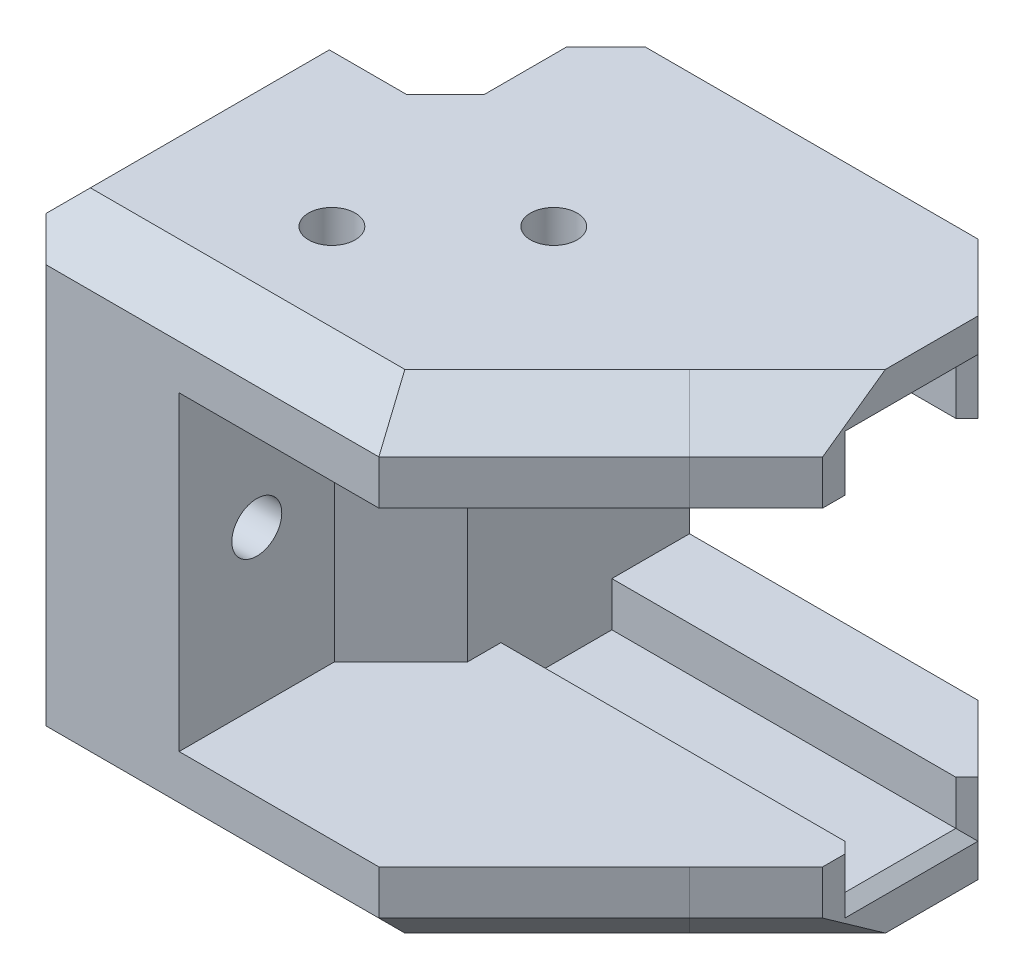
SolidWorks part; units mm, degrees
ref_plane "Front Plane" through (0, 0, 0) normal (0, 0, 1) x (1, 0, 0)
ref_plane "Top Plane" through (0, 0, 0) normal (0, 1, 0) x (1, 0, 0)
ref_plane "Right Plane" through (0, 0, 0) normal (1, 0, 0) x (0, 0, -1)
sketch "Sketch9" plane through (0, 0, 0) normal (0, 1, 0) x (1, 0, 0)
  line L1 (0, 0) -> (36, 0)
  line L2 (0, 0) -> (0, 36)
  line L3 (0, 36) -> (36, 36)
  line L4 (36, 0) -> (36, 36)
  dimension "D1" = 36
  dimension "D2" = 36
extrude "Boss-Extrude1" add sketch "Sketch9" along normal blind 40
chamfer "Chamfer2" distance 18 angle 45 1 edges at (0, 20, -36)
sketch "Sketch10" plane through (36, 0, 0) normal (1, 0, 0) x (0, 0, -1)
  line L4 (0, 0) -> (36, 0)
  line L5 (36, 0) -> (36, 40)
  line L6 (36, 40) -> (0, 40)
  line L7 (0, 40) -> (0, 0)
  line L8 (0, 0) -> (36, 0)
  line L9 (36, 0) -> (36, 40)
  line L10 (36, 40) -> (0, 40)
  line L11 (0, 40) -> (0, 0)
  dimension "D1" = 0
extrude "Boss-Extrude2" add sketch "Sketch10" along normal blind 8
sketch "Sketch12" plane through (0, 0, 0) normal (0, 0, 1) x (1, 0, 0)
  line L4 (0, 0) -> (44, 0)
  line L5 (44, 0) -> (44, 40)
  line L6 (44, 40) -> (0, 40)
  line L7 (0, 40) -> (0, 0)
  line L8 (0, 0) -> (44, 0)
  line L9 (44, 0) -> (44, 40)
  line L10 (44, 40) -> (0, 40)
  line L11 (0, 40) -> (0, 0)
  dimension "D1" = 0
extrude "Boss-Extrude3" add sketch "Sketch12" along normal blind 8
chamfer "Chamfer3" distance 18 angle 45 2 edges at (0, 20, 8) (44, 20, -36)
chamfer "Chamfer4" distance 6 angle 45 1 edges at (44, 20, 8)
sketch "Sketch13" plane through (23, 0, 23) normal (0.7071, 0, 0.7071) x (0.7071, 0, -0.7071)
  line L0 (7.0711, 40) -> (7.0711, 0) construction
  line L1 (7.0711, 32) -> (43.8406, 32)
  line L2 (7.0711, 32) -> (7.0711, 12)
  line L3 (7.0711, 12) -> (43.8406, 12)
  line L4 (43.8406, 32) -> (43.8406, 12)
  line L5 (43.8406, 0) -> (43.8406, 40) construction
  dimension "D1" = 8
  dimension "D2" = 20
extrude "Cut-Extrude6" cut sketch "Sketch13" against normal up to vertex (39.598 mm away) up to point (0, 40, -10)
sketch "Sketch22" plane through (-9, 0, -9) normal (-0.7071, 0, -0.7071) x (-0.7071, 0, 0.7071)
  line L0 (-38.1838, 40) -> (-12.7279, 40) construction
  circle A0 centre (-15.4558, 36) radius 2.1
  circle A1 centre (-35.4558, 36) radius 2.1
  circle A2 centre (-35.4558, 4) radius 2.1
  circle A3 centre (-15.4558, 4) radius 2.1
  point P16 (-25.4558, 40)
  dimension "D5" = 4.2
  dimension "D1" = 4
  dimension "D2" = 20
  dimension "D3" = 10
  dimension "D4" = 32
extrude "Cut-Extrude13" cut sketch "Sketch22" against normal blind 6
sketch "Sketch23" plane through (0, 40, 0) normal (0, 1, 0) x (1, 0, 0)
  line L0 (26, 36) -> (44, 36)
  line L1 (44, 36) -> (44, 18)
  line L2 (26, 36) -> (44, 18)
extrude "Boss-Extrude7" add sketch "Sketch23" against normal blind 8
sketch "Sketch24" plane through (0, 0, 0) normal (0, -1, 0) x (-1, 0, 0)
  line L0 (-44, 18) -> (-26, 36)
  line L1 (-26, 36) -> (-44, 36)
  line L2 (-44, 36) -> (-44, 18)
extrude "Boss-Extrude8" add sketch "Sketch24" against normal up to surface (12 mm away) up to face at (28.3333, 12, -7.6667)
sketch "Sketch25" plane through (0, 40, 0) normal (0, 1, 0) x (1, 0, 0)
  line L7 (18, -8) -> (38, -8)
  line L8 (38, -8) -> (44, -2)
  line L9 (44, -2) -> (44, 36)
  line L10 (44, 36) -> (18, 36)
  line L11 (18, 36) -> (0, 18)
  line L12 (0, 18) -> (0, 10)
  line L13 (0, 10) -> (18, -8)
  line L14 (18, -8) -> (38, -8)
  line L15 (38, -8) -> (44, -2)
  line L16 (44, -2) -> (44, 36)
  line L17 (44, 36) -> (18, 36)
  line L18 (18, 36) -> (0, 18)
  line L19 (0, 18) -> (0, 10)
  line L20 (0, 10) -> (18, -8)
  dimension "D1" = 0
extrude "Boss-Extrude9" add sketch "Sketch25" along normal blind 4
sketch "Sketch26" plane through (0, 32, 0) normal (0, -1, 0) x (-1, 0, 0)
  line L6 (-44, 36) -> (-44, -2)
  line L7 (-44, -2) -> (-38, -8)
  line L8 (-38, -8) -> (-18, -8)
  line L9 (-18, -8) -> (0, 10)
  line L10 (0, 10) -> (-26, 36)
  line L11 (-26, 36) -> (-44, 36)
  line L12 (-44, 36) -> (-44, -2)
  line L13 (-44, -2) -> (-38, -8)
  line L14 (-38, -8) -> (-18, -8)
  line L15 (-18, -8) -> (0, 10)
  line L16 (0, 10) -> (-26, 36)
  line L17 (-26, 36) -> (-44, 36)
  dimension "D1" = 0
extrude "Cut-Extrude14" cut sketch "Sketch26" against normal blind 4
sketch "Sketch27" plane through (0, 12, 0) normal (0, 1, 0) x (1, 0, 0)
  line L6 (44, -2) -> (44, 36)
  line L7 (44, 36) -> (26, 36)
  line L8 (26, 36) -> (0, 10)
  line L9 (0, 10) -> (18, -8)
  line L10 (18, -8) -> (38, -8)
  line L11 (38, -8) -> (44, -2)
  line L12 (44, -2) -> (44, 36)
  line L13 (44, 36) -> (26, 36)
  line L14 (26, 36) -> (0, 10)
  line L15 (0, 10) -> (18, -8)
  line L16 (18, -8) -> (38, -8)
  line L17 (38, -8) -> (44, -2)
  dimension "D1" = 0
extrude "Cut-Extrude15" cut sketch "Sketch27" against normal blind 4
sketch "Sketch28" plane through (0, 0, -36) normal (0, 0, -1) x (-1, 0, 0)
  line L1 (-26, 36) -> (-22, 36)
  line L2 (-26, 36) -> (-26, 8)
  line L3 (-26, 8) -> (-22, 8)
  line L4 (-22, 36) -> (-22, 8)
  dimension "D1" = 4
extrude "Cut-Extrude16" cut sketch "Sketch28" against normal through all
sketch "Sketch30" plane through (0, 8, 0) normal (0, 1, 0) x (1, 0, 0)
  line L0 (0, 10) -> (22, 10)
  line L1 (22, 10) -> (22, 32)
  line L2 (22, 32) -> (0, 10)
extrude "Boss-Extrude11" add sketch "Sketch30" along normal up to surface (28 mm away) up to face at (19.5314, 36, -18.602)
sketch "Sketch31" plane through (44, 0, 0) normal (1, 0, 0) x (0, 0, -1)
  line L1 (19, 40) -> (29, 40)
  line L2 (19, 40) -> (19, 4)
  line L3 (19, 4) -> (29, 4)
  line L4 (29, 40) -> (29, 4)
  dimension "D1" = 10
  dimension "D2" = 7
  dimension "D3" = 4
  dimension "D4" = 4
extrude "Cut-Extrude17" cut sketch "Sketch31" against normal up to surface (22 mm away) up to face at (22, 22, -23)
sketch "Sketch32" plane through (0, 0, 0) normal (0, -1, 0) x (-1, 0, 0)
  line L0 (-44, -2) -> (-44, 36) construction
  line L1 (0, 10) -> (-44, 10)
  line L2 (0, 10) -> (0, -8.0269)
  line L3 (0, -8.0269) -> (-44, -8.0269)
  line L4 (-44, 10) -> (-44, -8.0269)
extrude "Cut-Extrude18" cut sketch "Sketch32" against normal through all
sketch "Sketch33" plane through (44, 0, 0) normal (1, 0, 0) x (0, 0, -1)
  line L8 (10, 8) -> (10, 0)
  line L9 (10, 0) -> (36, 0)
  line L10 (36, 0) -> (36, 8)
  line L11 (36, 8) -> (29, 8)
  line L12 (29, 8) -> (29, 4)
  line L13 (29, 4) -> (19, 4)
  line L14 (19, 4) -> (19, 8)
  line L15 (19, 8) -> (10, 8)
  line L16 (10, 8) -> (10, 0)
  line L17 (10, 0) -> (36, 0)
  line L18 (36, 0) -> (36, 8)
  line L19 (36, 8) -> (29, 8)
  line L20 (29, 8) -> (29, 4)
  line L21 (29, 4) -> (19, 4)
  line L22 (19, 4) -> (19, 8)
  line L23 (19, 8) -> (10, 8)
  dimension "D1" = 0
extrude "Boss-Extrude12" add sketch "Sketch33" along normal blind 10
sketch "Sketch35" plane through (44, 0, 0) normal (1, 0, 0) x (0, 0, -1)
  line L8 (10, 44) -> (10, 36)
  line L9 (10, 36) -> (19, 36)
  line L10 (19, 36) -> (19, 40)
  line L11 (19, 40) -> (29, 40)
  line L12 (29, 40) -> (29, 36)
  line L13 (29, 36) -> (36, 36)
  line L14 (36, 36) -> (36, 44)
  line L15 (36, 44) -> (10, 44)
  line L16 (10, 44) -> (10, 36)
  line L17 (10, 36) -> (19, 36)
  line L18 (19, 36) -> (19, 40)
  line L19 (19, 40) -> (29, 40)
  line L20 (29, 40) -> (29, 36)
  line L21 (29, 36) -> (36, 36)
  line L22 (36, 36) -> (36, 44)
  line L23 (36, 44) -> (10, 44)
  dimension "D1" = 0
extrude "Boss-Extrude13" add sketch "Sketch35" along normal blind 10
chamfer "Chamfer5" distance 6 angle 45 4 edges at (54, 4, -36) (54, 4, -10) (54, 40, -36) (54, 40, -10)
sketch "Sketch36" plane through (0, 44, 0) normal (0, 1, 0) x (1, 0, 0)
  line L0 (14, 32) -> (14, 26)
  line L1 (18, 36) -> (0, 18) construction
  line L2 (14, 26) -> (10, 22)
  line L3 (10, 22) -> (4, 22)
  line L4 (4, 22) -> (14, 32)
  dimension "D1" = 4
  dimension "D2" = 4
  dimension "D3" = 6
extrude "Cut-Extrude19" cut sketch "Sketch36" against normal through all
chamfer "Chamfer6" distance 6 angle 45 1 edges at (22, 22, -10)
sketch "Sketch37" plane through (22, 0, 0) normal (1, 0, 0) x (0, 0, -1)
  circle A0 centre (24, 31) radius 2.8
  circle A1 centre (24, 13) radius 2.8
  dimension "D4" = 5.6
  dimension "D1" = 5
  dimension "D2" = 9
  dimension "D3" = 9
extrude "Cut-Extrude20" cut sketch "Sketch37" against normal blind 7
sketch "Sketch39" plane through (0, 0, -10) normal (0, 0, 1) x (1, 0, 0)
  line L8 (48, 8) -> (16, 8)
  line L9 (16, 8) -> (16, 36)
  line L10 (16, 36) -> (48, 36)
  line L11 (48, 36) -> (48, 44)
  line L12 (48, 44) -> (0, 44)
  line L13 (0, 44) -> (0, 0)
  line L14 (0, 0) -> (48, 0)
  line L15 (48, 0) -> (48, 8)
  line L16 (48, 8) -> (16, 8)
  line L17 (16, 8) -> (16, 36)
  line L18 (16, 36) -> (48, 36)
  line L19 (48, 36) -> (48, 44)
  line L20 (48, 44) -> (0, 44)
  line L21 (0, 44) -> (0, 0)
  line L22 (0, 0) -> (48, 0)
  line L23 (48, 0) -> (48, 8)
  dimension "D1" = 0
extrude "Boss-Extrude14" add sketch "Sketch39" along normal blind 14
chamfer "Chamfer7" distance 14 angle 45 2 edges at (48, 4, 4) (48, 40, 4)
chamfer "Chamfer8" distance 4 angle 45 7 edges at (51, 0, -13) (51, 44, -13) (41, 0, -3) (17, 0, 4) (0, 22, 4) (17, 44, 4) (41, 44, -3)
sketch "Sketch41" plane through (15, 0, 0) normal (1, 0, 0) x (0, 0, -1)
  circle A1 centre (24, 31) radius 2.8
  circle A2 centre (24, 31) radius 2.8
  dimension "D1" = 0
extrude "Boss-Extrude15" add sketch "Sketch41" along normal up to surface (7 mm away) up to face at (22, 33.8, -24)
sketch "Sketch42" plane through (15, 0, 0) normal (1, 0, 0) x (0, 0, -1)
  circle A1 centre (24, 13) radius 2.8
  circle A2 centre (24, 13) radius 2.8
  dimension "D1" = 0
extrude "Boss-Extrude16" add sketch "Sketch42" along normal up to surface (7 mm away) up to face at (22, 15.8, -24)
chamfer "Chamfer9" distance 1 angle 45 6 edges at (54, 6, -19) (54, 4, -24) (54, 6, -29) (54, 38, -29) (54, 40, -24) (54, 38, -19)
sketch "Sketch43" plane through (16, 0, 0) normal (1, 0, 0) x (0, 0, -1)
  circle A0 centre (3, 22) radius 2.25
  dimension "D1" = 4.5
  dimension "D2" = 14
  dimension "D3" = 7
extrude "Cut-Extrude21" cut sketch "Sketch43" against normal through all
sketch "Sketch44" plane through (0, 0, 0) normal (-1, 0, 0) x (0, 0, 1)
  circle A0 centre (-3, 22) radius 4
  dimension "D1" = 8
extrude "Cut-Extrude22" cut sketch "Sketch44" against normal blind 7
chamfer "Chamfer10" distance 4 angle 45 1 edges at (0, 22, -7)
chamfer "Chamfer11" distance 4 angle 45 1 edges at (0, 44, -9)
chamfer "Chamfer12" distance 3 angle 45 1 edges at (0, 0, -9)
sketch "Sketch48" plane through (0, 0, 0) normal (0, -1, 0) x (-1, 0, 0)
  circle A0 centre (-28.0253, 18.0249) radius 2.1
  circle A1 centre (-18.0253, 8.0249) radius 2.1
  dimension "D1" = 4.2
extrude "Cut-Extrude26" cut sketch "Sketch48" against normal blind 4
sketch "Sketch49" plane through (0, 44, 0) normal (0, 1, 0) x (1, 0, 0)
  circle A0 centre (17.8984, 7.8684) radius 2.1
  circle A1 centre (27.8984, 17.8684) radius 2.1
  dimension "D1" = 4.2
extrude "Cut-Extrude27" cut sketch "Sketch49" against normal blind 4
sketch "Sketch50" plane through (0, 0, 0) normal (0, -1, 0) x (-1, 0, 0)
  line L0 (-3.5355, 21.5355) -> (-10.9289, 21.5355)
  line L2 (-10.9289, 21.5355) -> (-14.4645, 25.0711)
  line L3 (-14.4645, 25.0711) -> (-14.4645, 32.4645)
  line L4 (-14, 32) -> (-18, 36) construction
  line L5 (-14.4645, 32.4645) -> (-3.5355, 21.5355)
  point P2 (0, 0)
  point P3 (-3.5, 21.5)
  point P4 (-14.5402, 32.5402)
  point P9 (0, 0)
  point P13 (-14.4645, 32.4645)
  point P14 (-14.4645, 32.4645)
  point P15 (-3.5, 21.5)
  dimension "D1" = 5
  dimension "D2" = 5
  dimension "D3" = 5
extrude "Cut-Extrude28" cut sketch "Sketch50" against normal through all
